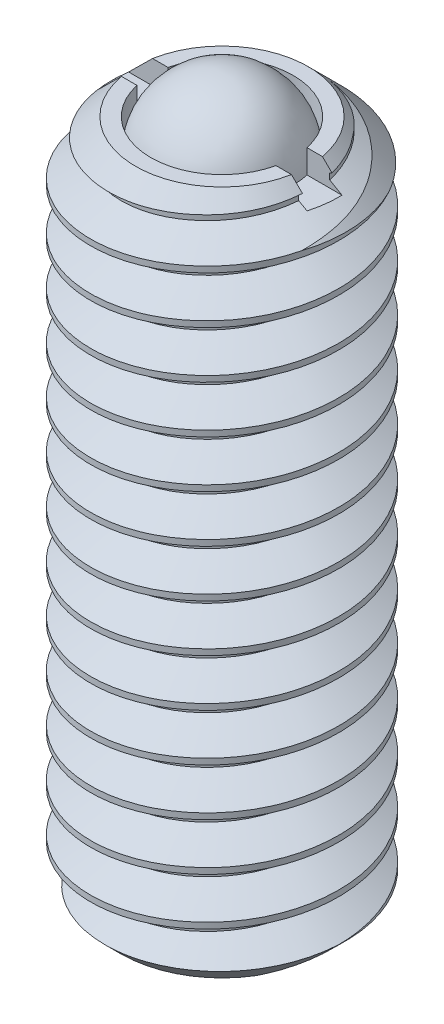
SolidWorks part; units mm, degrees
ref_plane "Front" through (0, 0, 0) normal (0, 0, 1) x (1, 0, 0)
ref_plane "Top" through (0, 0, 0) normal (0, 1, 0) x (1, 0, 0)
ref_plane "Right" through (0, 0, 0) normal (1, 0, 0) x (0, 0, -1)
sketch "Sketch24" plane through (0, 0, 0) normal (1, 0, 0) x (0, 0, -1)
  line L0 (2.0828, 5.6515) -> (-2.0828, 5.6515) construction
  line L1 (0, 5.6515) -> (2.0828, 5.6515)
  line L2 (0, 5.6515) -> (0, -5.6515)
  line L3 (0, -5.6515) -> (2.0828, -5.6515)
  line L4 (2.0828, 5.6515) -> (2.0828, -5.6515)
  point P5 (2.0828, 2.0796)
  dimension "Body Length" = 11.303
  dimension "Screw Dia" = 4.1656
  dimension "D1" = 3.5719
revolve "Revolve1" add sketch "Sketch24" angle 360 about L2
sketch "Sketch37" plane through (0, 5.6515, 0) normal (0, 1, 0) x (1, 0, 0)
  circle A1 centre (0, 0) radius 2.0828
  circle A2 centre (0, 0) radius 2.0828
  dimension "D1" = 0
curve "Helix/Spiral1" pitch 0.7937 height 12.0968 turns 15.24 parameters "pitch"=0.7937
sketch "Sketch38" plane through (0, 0, 0) normal (1, 0, 0) x (0, 0, -1)
  line L0 (-2.0828, 6.346) -> (-2.0828, 5.6515)
  line L1 (-2.0828, 6.346) -> (-1.5672, 6.0484)
  line L2 (-1.5672, 6.0484) -> (-1.5672, 5.9492)
  line L3 (-1.5672, 5.9492) -> (-2.0828, 5.6515)
  line L4 (-1.5672, 5.9988) -> (-2.0828, 5.9988) construction
  line L5 (-1.825, 6.1972) -> (-1.825, 5.8003) construction
  line L6 (2.0828, 5.6515) -> (-2.0828, 5.6515) construction
  line L7 (0, 0) -> (0, 5.6515) construction
  dimension "D2" = 0.3969
  dimension "D1" = 0.0992
  dimension "D3" = 60
  dimension "D4" = 0.5156
  dimension "D5" = 1.5672
sweep "Cut-Sweep1" cut profiles "Sketch38" path "Helix/Spiral1" align with end faces yes
sketch "Sketch26" plane through (0, 0, 0) normal (1, 0, 0) x (0, 0, -1)
  line L0 (0, -4.0513) -> (0, 5.6515)
  line L1 (0, 5.6515) -> (0, -5.6515) construction
  line L2 (0, 5.6515) -> (1.1938, 5.6515)
  line L3 (1.1938, 5.6515) -> (1.1938, -4.0513)
  line L5 (1.1938, -4.0513) -> (0, -4.0513)
  line L7 (1.1938, 5.6515) -> (-1.1938, 5.6515) construction
  line L8 (2.0828, 5.6515) -> (-2.0828, 5.6515) construction
  dimension "D1" = 1.6002
  dimension "Ball Dia" = 2.3876
revolve "Cut-Revolve10" cut sketch "Sketch26" angle 360 about L0
sketch "Sketch31" plane through (0, 0, 0) normal (1, 0, 0) x (0, 0, -1)
  line L0 (2.0828, -5.6515) -> (1.7018, -5.6515)
  line L1 (2.0828, 5.6515) -> (2.0828, -5.6515) construction
  line L3 (0, 0) -> (0, -14.5366) construction
  line L4 (1.7018, -5.6515) -> (2.0828, -5.2705)
  line L5 (0, 0) -> (2.0828, 0) construction
  line L14 (2.0828, 5.6515) -> (1.4478, 5.6515)
  line L15 (0, 5.6515) -> (2.0828, 5.6515) construction
  line L16 (1.4478, 5.6515) -> (2.0828, 5.0165)
  line L17 (2.0828, 5.0165) -> (2.0828, 5.6515)
  line L18 (2.0828, -5.2705) -> (2.0828, -5.6515)
  dimension "D1" = 0.254
  dimension "D2" = 45
  dimension "D3" = 0.254
revolve "Cut-Revolve13" cut sketch "Sketch31" angle 360 about L2
sketch "Sketch28" plane through (0, 0, 0) normal (1, 0, 0) x (0, 0, -1)
  line L0 (-2.0828, -5.2546) -> (0.2604, -5.2546) construction
  line L1 (-0.2604, -5.6515) -> (0.2604, -5.6515) construction
  line L2 (-0.2604, -5.6515) -> (-0.2604, -5.2546) construction
  line L3 (-0.2604, -5.2546) -> (0.2604, -5.2546) construction
  line L4 (0.2604, -5.6515) -> (0.2604, -5.2546) construction
  line L5 (2.0828, 5.6515) -> (-2.0828, 5.6515) construction
  line L6 (-0.2603, 5.6515) -> (0.2603, 5.6515)
  line L7 (-0.2603, 5.6515) -> (-0.2603, 5.2546)
  line L8 (-0.2603, 5.2546) -> (0.2603, 5.2546)
  line L9 (0.2603, 5.6515) -> (0.2603, 5.2546)
  line L11 (-1.7018, -5.6515) -> (1.7018, -5.6515) construction
  dimension "D1" = 0.5207
  dimension "D2" = 0.3969
extrude "Cut-Extrude11" cut sketch "Sketch28" against normal through all and the other way through all
sketch "Sketch27" plane through (0, 0, 0) normal (1, 0, 0) x (0, 0, -1)
  line L0 (0, 5.6515) -> (0, -5.6515) construction
  line L1 (1.1938, 5.6515) -> (1.1938, -4.0513) construction
  line L2 (0, -5.6515) -> (0, 3.8989) construction
  line L3 (0, 6.2865) -> (0, 3.8989)
  circle A0 centre (0, 5.0927) radius 1.1938 construction
  arc A1 (0, 6.2865) -> (0, 3.8989) centre (0, 5.0927) cw
  dimension "Ball Projection" = 0.635
revolve "Revolve2" add sketch "Sketch27" angle 360 about L3
ref_plane "Plane1" [suppressed] through (-7.9375, 0, 0) normal (1, 0, 0) x (0, 0, -1)
sketch "Sketch21" [suppressed] plane through (-7.9375, 0, 0) normal (1, 0, 0) x (0, 0, -1)
  line L0 (0, -1.7183) -> (0, -3.2804) construction
  line L2 (7.9375, 15.875) -> (-7.9375, 15.875) construction
  line L3 (0, 15.875) -> (0, -15.875) construction
  ellipse E0 centre (0, 2.3532) end of major axis (0, -2.8062) minor radius 3.9688
  dimension "D5" = 2.0828
  dimension "D6" = 2.7076
  dimension "D7" = 2.8746
sketch "Sketch41" [suppressed] plane through (-7.9375, 0, 0) normal (1, 0, 0) x (0, 0, -1)
  ellipse E1 centre (0, 2.3532) end of major axis (0, 7.5125) minor radius 3.9688
  ellipse E2 centre (0, 2.3532) end of major axis (0, 7.5125) minor radius 3.9688
  dimension "D1" = 0
sketch "Sketch43" [suppressed] plane through (0, 0, 0) normal (1, 0, 0) x (0, 0, -1)
  ellipse E1 centre (0, 2.3532) end of major axis (0, 7.5125) minor radius 3.9688
  ellipse E2 centre (0, 2.3532) end of major axis (0, 7.5125) minor radius 3.9688
  dimension "D1" = 0
extrude "Extrude9" [suppressed] cut sketch "Sketch43" against normal through all
sketch "Sketch44" [suppressed] plane through (0, 0, 0) normal (1, 0, 0) x (0, 0, -1)
  ellipse E1 centre (0, 2.3532) end of major axis (0, 7.5125) minor radius 3.9688
  ellipse E2 centre (0, 2.3532) end of major axis (0, 7.5125) minor radius 3.9688
  dimension "D1" = 0
extrude "Extrude10" [suppressed] add sketch "Sketch44" against normal blind 1.5672 separate body
dome "Dome1" [suppressed] faces to dome 1 distance 0.2578 parameters "D1"=0.2578
sketch "Sketch45" plane through (0, 0, 0) normal (0, 1, 0) x (1, 0, 0)
  circle A0 centre (0, 0) radius 1.1938
  arc A1 (-1.1651, -0.2603) -> (1.1651, -0.2603) centre (0, 0) ccw construction
extrude "Extrude11" [suppressed] cut sketch "Sketch45" against normal through all and the other way through all
sketch "Sketch46" plane through (0, -5.6515, 0) normal (0, -1, 0) x (1, 0, 0)
  line L1 (-0.8001, 0.4619) -> (-0.8001, -0.4619)
  line L2 (-0.8001, -0.4619) -> (0, -0.9239)
  line L3 (0, -0.9239) -> (0.8001, -0.4619)
  line L4 (0.8001, -0.4619) -> (0.8001, 0.4619)
  line L5 (0.8001, 0.4619) -> (0, 0.9239)
  line L6 (0, 0.9239) -> (-0.8001, 0.4619)
  circle A0 centre (0, 0) radius 0.8001 construction
  dimension "Hex" = 1.6002
extrude "Extrude12" cut sketch "Sketch46" against normal blind 0.8001
sketch "Sketch47" plane through (0, -5.6515, 0) normal (0, -1, 0) x (1, 0, 0)
  circle A0 centre (0, 0) radius 0.9239
extrude "Extrude13" cut sketch "Sketch47" against normal blind 0.8001 draft 60
equation "\"D1@Sketch26\" = \"Hex@Sketch46\""
equation "\"D1@Sketch28\" = \"Screw Dia@Sketch24\"/8"
equation "\"D1@Sketch38\" = \"pitch@Helix/Spiral1\"*.125"
equation "\"D2@Sketch38\" = \"pitch@Helix/Spiral1\"*.50"
equation "\"D3@Helix/Spiral1\" = \"Body Length@Sketch24\"+\"pitch@Helix/Spiral1\""
equation "\"D5@Sketch21\" = \"Screw Dia@Sketch24\"*.50"
equation "\"D6@Sketch21\" = \"D5@Sketch21\"*1.3"
equation "\"D7@Sketch21\" = \"pitch@Helix/Spiral1\"*3.62154"
equation "\"D1@Sketch24\" = \"pitch@Helix/Spiral1\"*4.50"
equation "\"D1@Plane1\" = \"Screw Dia@Sketch24\"/2"
equation "\"D1@Extrude10\" = \"D5@Sketch38\""
equation "\"D1@Dome1\" = \"D6@Sketch38\""
equation "\"D2@Sketch28\" = \"pitch@Helix/Spiral1\"/2"
equation "\"D1@Extrude12\" = \"Hex@Sketch46\"/2"
equation "\"D1@Extrude13\" = \"Hex@Sketch46\"/2"
